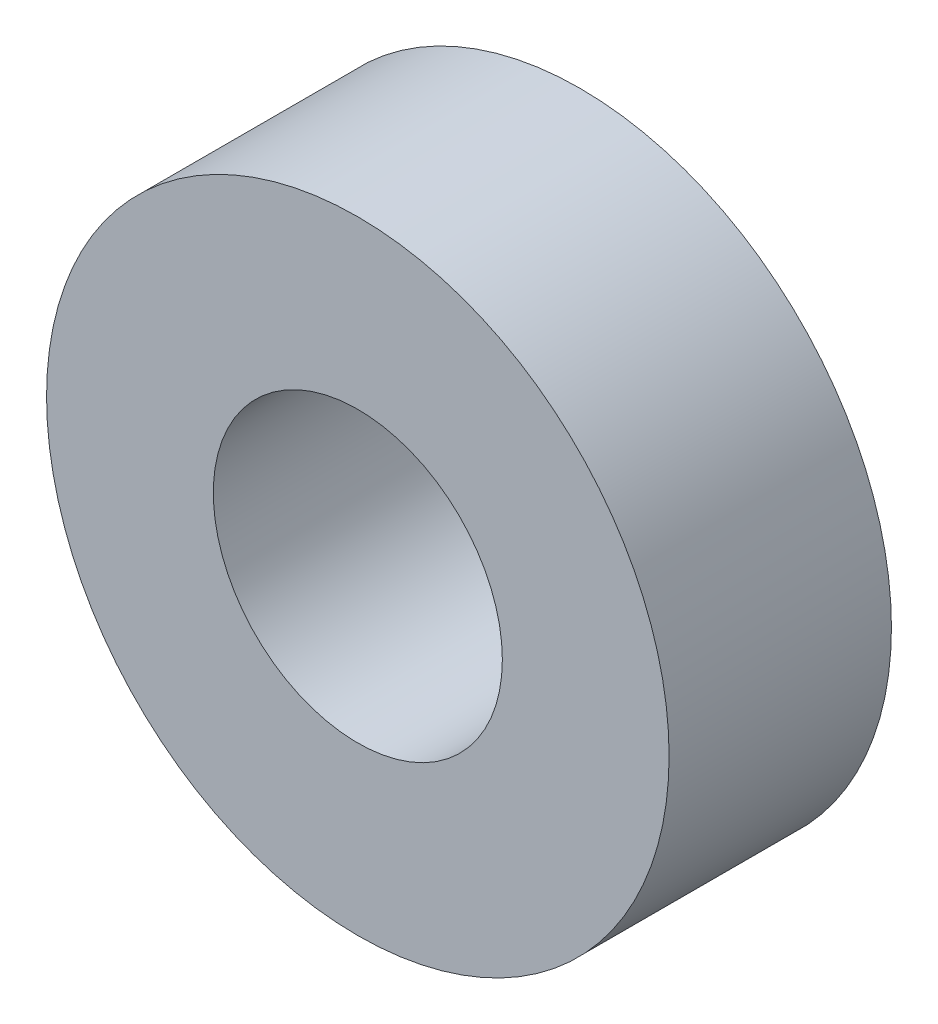
SolidWorks part; units mm, degrees
ref_plane "Plan de face" through (0, 0, 0) normal (0, 0, 1) x (1, 0, 0)
ref_plane "Plan de dessus" through (0, 0, 0) normal (0, 1, 0) x (1, 0, 0)
ref_plane "Plan de droite" through (0, 0, 0) normal (1, 0, 0) x (0, 0, -1)
sketch "Esquisse1" plane through (0, 0, 0) normal (0, 0, 1) x (1, 0, 0)
  line L1 (-0.9885, -3.25) -> (1.037, -3.25) construction
  circle A0 centre (0, 0) radius 7
  circle A1 centre (0, 0) radius 3.25
  dimension "D1" = 14
  dimension "D2" = 6.5
extrude "Boss.-Extru.1" add sketch "Esquisse1" along normal blind 5
